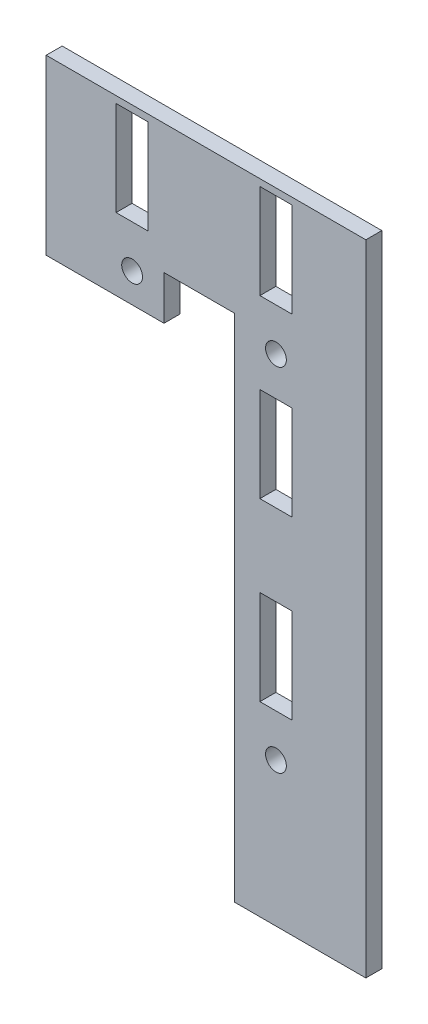
SolidWorks part; units mm, degrees
ref_plane "Front Plane" through (0, 0, 0) normal (1, 0, 0) x (0, 1, 0)
ref_plane "Top Plane" through (0, 0, 0) normal (0, 0, 1) x (0, 1, 0)
ref_plane "Right Plane" through (0, 0, 0) normal (0, 1, 0) x (-1, 0, 0)
sketch "Sketch1" plane through (0, 0, 0) normal (0, 0, 1) x (0, 1, 0)
  line L1 (-50.8, 25.4) -> (50.8, 25.4)
  line L2 (-50.8, 25.4) -> (-50.8, -25.4)
  line L3 (-50.8, -25.4) -> (50.8, -25.4)
  line L4 (50.8, 25.4) -> (50.8, -25.4)
  line L5 (-50.8, 25.4) -> (50.8, -25.4) construction
  line L6 (-50.8, -25.4) -> (50.8, 25.4) construction
  point P0 (0, 0)
  dimension "D1" = 101.6
  dimension "D2" = 50.8
extrude "Boss-Extrude1" add sketch "Sketch1" along normal blind 2.54
sketch "Sketch2" plane through (0, 0, 2.54) normal (0, 0, 1) x (1, 0, 0)
  line L0 (11.1159, -27.94) -> (11.1159, 27.94) construction
  line L1 (11.1159, 27.94) -> (-11.7441, 27.94) construction
  line L2 (-11.7441, 27.94) -> (-11.7441, -27.94) construction
  line L3 (-11.7441, -27.94) -> (11.1159, -27.94) construction
  line L4 (25.4, 50.8) -> (-25.4, 50.8) construction
  circle A0 centre (11.1159, 27.94) radius 1.651
  circle A1 centre (11.1159, -27.94) radius 1.651
  circle A2 centre (-11.7441, 27.94) radius 1.651
  dimension "D3" = 3.302
  dimension "D1" = 55.88
  dimension "D2" = 22.86
  dimension "D4" = 22.86
extrude "Cut-Extrude1" cut sketch "Sketch2" against normal through all
sketch "Sketch3" plane through (0, 0, 2.54) normal (0, 0, 1) x (1, 0, 0)
  line L0 (11.1159, -27.94) -> (11.1159, 27.94) construction
  line L1 (13.6659, -6.16) -> (8.5659, -6.16)
  line L2 (13.6659, -6.16) -> (13.6659, -21.18)
  line L3 (13.6659, -21.18) -> (8.5659, -21.18)
  line L4 (8.5659, -6.16) -> (8.5659, -21.18)
  line L5 (13.6659, -6.16) -> (8.5659, -21.18) construction
  line L6 (13.6659, -21.18) -> (8.5659, -6.16) construction
  line L7 (13.6659, 6.76) -> (8.5659, 6.76)
  line L8 (13.6659, 6.76) -> (13.6659, 21.78)
  line L9 (13.6659, 21.78) -> (8.5659, 21.78)
  line L10 (8.5659, 6.76) -> (8.5659, 21.78)
  line L11 (13.6659, 6.76) -> (8.5659, 21.78) construction
  line L12 (13.6659, 21.78) -> (8.5659, 6.76) construction
  line L13 (13.6659, 34.7) -> (8.5659, 34.7)
  line L14 (13.6659, 34.7) -> (13.6659, 49.72)
  line L15 (13.6659, 49.72) -> (8.5659, 49.72)
  line L16 (8.5659, 34.7) -> (8.5659, 49.72)
  line L17 (13.6659, 34.7) -> (8.5659, 49.72) construction
  line L18 (13.6659, 49.72) -> (8.5659, 34.7) construction
  line L19 (-9.1941, 34.7) -> (-14.2941, 34.7)
  line L20 (-9.1941, 34.7) -> (-9.1941, 49.72)
  line L21 (-9.1941, 49.72) -> (-14.2941, 49.72)
  line L22 (-14.2941, 34.7) -> (-14.2941, 49.72)
  line L23 (-9.1941, 34.7) -> (-14.2941, 49.72) construction
  line L24 (-9.1941, 49.72) -> (-14.2941, 34.7) construction
  circle A0 centre (11.1159, -27.94) radius 1.651 construction
  point P0 (11.1159, -13.67)
  point P10 (11.1159, 14.27)
  point P14 (11.1159, 42.21)
  point P19 (-11.7441, 42.21)
  point P24 (0, 0)
  dimension "D1" = 6.76
  dimension "D3" = 15.02
  dimension "D4" = 27.94
  dimension "D5" = 27.94
  dimension "D6" = 22.86
  dimension "D7" = 5.1
extrude "Cut-Extrude4" cut sketch "Sketch3" against normal through all
sketch "Sketch5" plane through (0, 0, 2.54) normal (0, 0, 1) x (1, 0, 0)
  line L0 (4.5019, -50.8) -> (4.5019, 30.255)
  line L1 (-25.4, -50.8) -> (25.4, -50.8) construction
  line L2 (4.5019, 30.255) -> (-6.6741, 30.255)
  line L3 (-6.6741, 30.255) -> (-6.6741, 23.27)
  line L4 (-6.6741, 23.27) -> (-25.4, 23.27)
  line L5 (-25.4, 50.8) -> (-25.4, -50.8) construction
  line L6 (-25.4, 23.27) -> (-25.4, -50.8)
  line L7 (-25.4, -50.8) -> (4.5019, -50.8)
  dimension "D1" = 4.064
  dimension "D2" = 4.445
  dimension "D3" = 11.43
  dimension "D4" = 15.24
extrude "Cut-Extrude5" cut sketch "Sketch5" against normal through all
